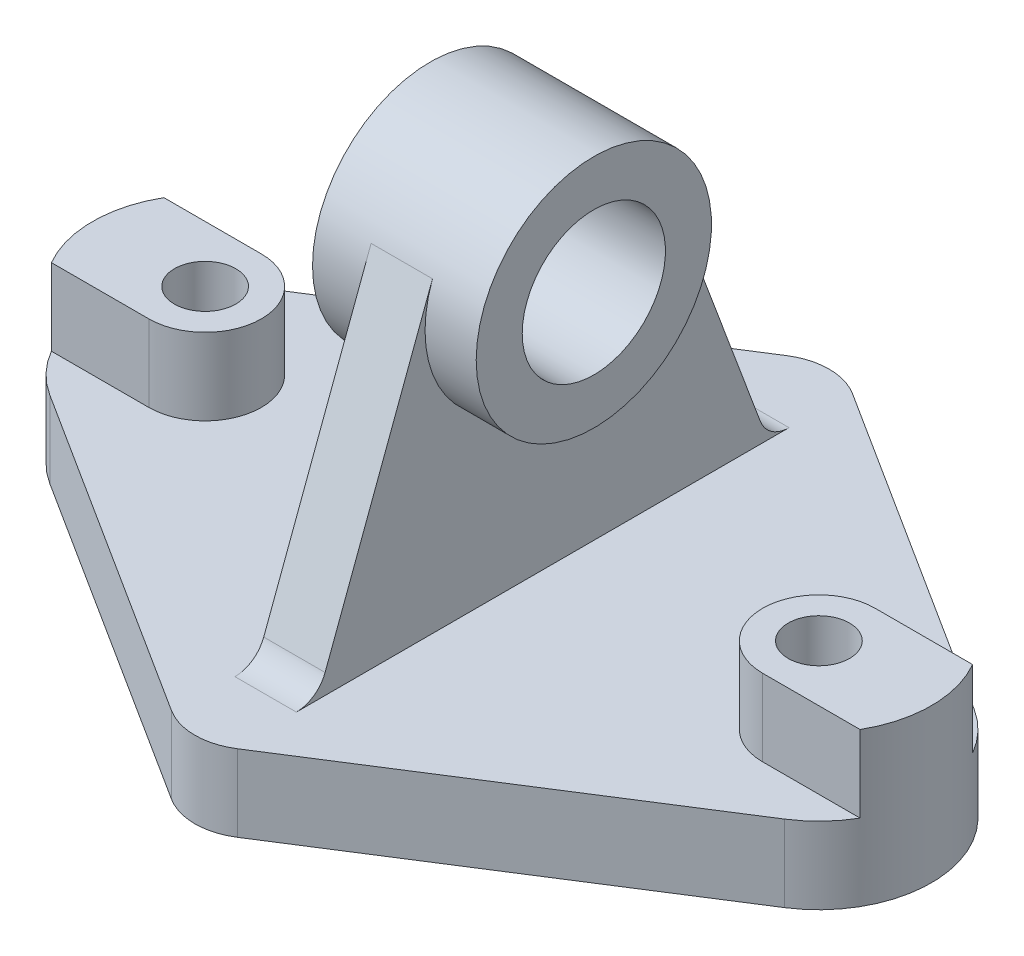
SolidWorks part; units mm, degrees
ref_plane "Front Plane" through (0, 0, 0) normal (0, 0, 1) x (1, 0, 0)
ref_plane "Top Plane" through (0, 0, 0) normal (0, 1, 0) x (1, 0, 0)
ref_plane "Right Plane" through (0, 0, 0) normal (1, 0, 0) x (0, 0, -1)
sketch "Sketch1" plane through (0, 0, 0) normal (0, 1, 0) x (1, 0, 0)
  line L0 (0, 62) -> (0, -62)
  line L1 (6.4387, 60.1264) -> (71.8042, 18.565)
  line L3 (0, 0) -> (82, 0) construction
  line L4 (6.4387, -60.1264) -> (71.8042, -18.565)
  line L5 (60, 11) -> (79.0526, 11)
  line L6 (60, -11) -> (79.0526, -11)
  arc A0 (71.8042, -18.565) -> (71.8042, 18.565) centre (60, 0) ccw
  arc A1 (6.4387, 60.1264) -> (0, 62) centre (0, 50) ccw
  arc A2 (6.4387, -60.1264) -> (0, -62) centre (0, -50) cw
  arc A3 (60, 11) -> (60, -11) centre (60, 0) ccw
  circle A4 centre (60, 0) radius 6
  dimension "D1" = 44
  dimension "D3" = 24
  dimension "D5" = 22
  dimension "D7" = 12
  dimension "D2" = 60
  dimension "D4" = 124
  dimension "D6" = 60
extrude "Boss-Extrude1" add sketch "Sketch1" along normal blind 30 contours A3 L3 A4 A0 L5 | L3 A3 L6 A0 A4 region at (67.3949, 0, -5.7175) region at (67.3949, 0, 5.7175)
extrude "Boss-Extrude2" add sketch "Sketch1<3>" along normal blind 15 contours L0 L3 A3 L5 A0 L1 A1 | L3 L0 A2 L4 A0 L6 A3 region at (27.2652, 0, -24.0492) region at (27.2652, 0, 24.0492)
sketch "Sketch1<3>" plane through (0, 0, 0) normal (0, 1, 0) x (1, 0, 0) same geometry as "Sketch1"
sketch "Sketch2" plane through (0, 0, 0) normal (-1, 0, 0) x (0, 0, 1)
  line L0 (0, 0) -> (0, 67) construction
  line L1 (21.5431, 75.0557) -> (44, 15)
  line L2 (-21.5431, 75.0557) -> (-44, 15)
  line L3 (-62, 15) -> (62, 15) construction
  line L4 (-62, 0) -> (62, 0) construction
  line L5 (-44, 15) -> (44, 15)
  circle A0 centre (0, 67) radius 14
  circle A1 centre (0, 67) radius 23
  line M4 (62, 15) -> (-62, 15)
  dimension "D1" = 28
  dimension "D2" = 46
  dimension "D3" = 88
  dimension "D4" = 44
  dimension "D5" = 67
extrude "Boss-Extrude3" add sketch "Sketch2" against normal blind 6 contours L5 L0 A1 L2 | L0 L1 A1 M4 region at (0, 32.9715, -19.9908) region at (0, 32.9715, 19.9908)
extrude "Boss-Extrude4" add sketch "Sketch2<3>" against normal blind 16 contours A1 A0 region at (0, 70.9774, 21.9927)
sketch "Sketch2<3>" plane through (0, 0, 0) normal (-1, 0, 0) x (0, 0, 1) same geometry as "Sketch2"
fillet "Fillet1" radius 6 2 edges at (3, 15, -44) (3, 15, 44)
mirror "Mirror1" about plane through (0, 15, 0) normal (1, 0, 0) of bodies 104
